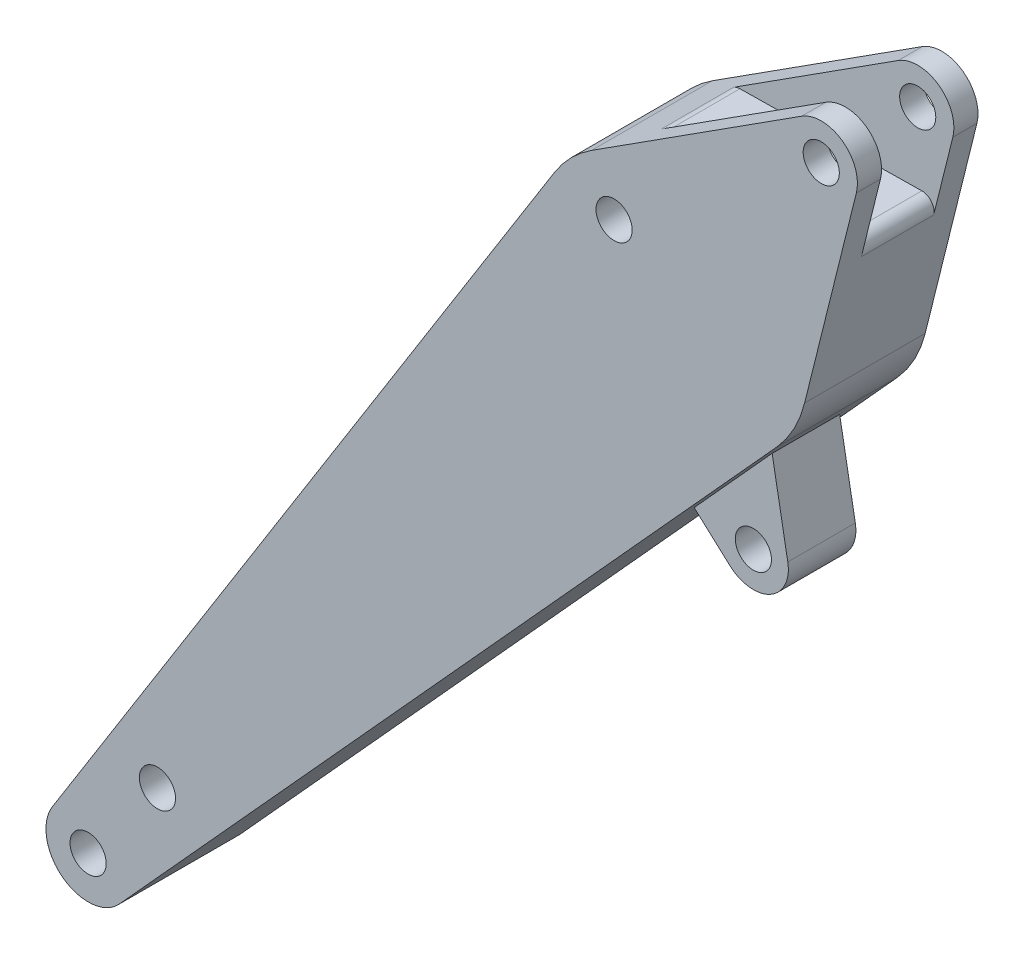
SolidWorks part; units mm, degrees
ref_plane "前视基准面" through (0, 0, 0) normal (0, 0, 1) x (1, 0, 0)
ref_plane "上视基准面" through (0, 0, 0) normal (0, 1, 0) x (1, 0, 0)
ref_plane "右视基准面" through (0, 0, 0) normal (1, 0, 0) x (0, 0, -1)
sketch "草图1" plane through (0, 0, 0) normal (0, 0, 1) x (1, 0, 0)
  line L0 (84.9524, 101.1252) -> (168.9456, 46.856) construction
  line L1 (255.3141, 96.6057) -> (199.0919, 34.648)
  line L2 (255.3141, 96.6057) -> (260.2111, 116.2752)
  line L3 (255.6812, 119.5257) -> (236.3769, 107.1531)
  line L4 (236.3769, 107.1531) -> (193.5351, 38.8599)
  line L5 (257.3, 117) -> (196.5, 37) construction
  line L6 (236.3769, 107.1531) -> (244.8958, 100.6787) construction
  line L7 (255.3141, 96.6057) -> (247.3161, 103.8633) construction
  line L8 (196.5, 37) -> (257.3, 37) construction
  line L9 (257.3, 37) -> (257.3, 117) construction
  arc A0 (193.5351, 38.8599) -> (199.0919, 34.648) centre (196.5, 37) ccw
  arc A1 (255.6812, 119.5257) -> (260.2111, 116.2752) centre (257.3, 117) cw
  circle A4 centre (196.5, 37) radius 1.5
  circle A5 centre (202.2483, 44.5635) radius 1.5
  circle A6 centre (257.3, 117) radius 1.5
  circle A7 centre (240.1188, 104.3092) radius 1.5
  dimension "D2" = 3
  dimension "D3" = 16.5
  dimension "D4" = 3
  dimension "D5" = 3.5
  dimension "D1" = 100
  dimension "D6" = 4
  dimension "D7" = 10.7
  dimension "D8" = 10.8
  dimension "D9" = 80
  dimension "D10" = 9.5
  dimension "D11" = 196.5
  dimension "D12" = 37
  dimension "D13" = 60.8
  dimension "D14" = 6
extrude "凸台-拉伸1" add sketch "草图1" along normal blind 5 and the other way blind 5
sketch "草图2" plane through (0, 0, 0) normal (0, 0, 1) x (1, 0, 0)
  line L0 (242.2703, 110.9303) -> (258.938, 111.1614)
  line L1 (255.6812, 119.5257) -> (236.3769, 107.1531) construction
  line L2 (255.3141, 96.6057) -> (260.2111, 116.2752) construction
  line L7 (199.0919, 34.648) -> (255.3141, 96.6057)
  line L8 (255.3141, 96.6057) -> (260.2111, 116.2752)
  line L9 (255.6812, 119.5257) -> (236.3769, 107.1531)
  line L10 (236.3769, 107.1531) -> (193.5351, 38.8599)
  line L11 (199.0919, 34.648) -> (255.3141, 96.6057)
  line L12 (255.3141, 96.6057) -> (260.2111, 116.2752)
  line L13 (255.6812, 119.5257) -> (236.3769, 107.1531)
  line L14 (236.3769, 107.1531) -> (193.5351, 38.8599)
  circle A0 centre (257.3, 117) radius 1.5 construction
  circle A1 centre (257.3, 117) radius 1.5
  arc A4 (193.5351, 38.8599) -> (199.0919, 34.648) centre (196.5, 37) ccw
  arc A6 (260.2111, 116.2752) -> (255.6812, 119.5257) centre (257.3, 117) ccw
  arc A8 (193.5351, 38.8599) -> (199.0919, 34.648) centre (196.5, 37) ccw
  arc A10 (260.2111, 116.2752) -> (255.6812, 119.5257) centre (257.3, 117) ccw
  dimension "D2" = 7
  dimension "D3" = 15
  dimension "D1" = 0
extrude "切除-拉伸1" cut sketch "草图2" against normal blind 3 and the other way blind 3 contours L12 A10 L13 L0 A1 region at (253.3987, 114.3214, 0)
sketch "草图3" plane through (0, 0, 0) normal (0, 0, 1) x (1, 0, 0)
  line L0 (244.5601, 84.7547) -> (247.5223, 82.0667)
  line L1 (199.0919, 34.648) -> (255.3141, 96.6057) construction
  line L2 (251.0285, 91.8829) -> (252.3246, 84.7315)
  line L3 (244.5601, 84.7547) -> (251.0285, 91.8829)
  circle A0 centre (249.4711, 84.2143) radius 1.5
  arc A1 (247.5223, 82.0667) -> (252.3246, 84.7315) centre (249.4711, 84.2143) ccw
  dimension "D1" = 3
  dimension "D2" = 2.9
  dimension "D3" = 4
extrude "凸台-拉伸4" add sketch "草图3" along normal blind 2.8 and the other way blind 2.8
fillet "圆角1" radius 10 2 edges at (255.3141, 96.6057, 0) (236.3769, 107.1531, 0)
fillet "圆角2" radius 1 2 edges at (258.938, 111.1614, 0) (242.2703, 110.9303, 0)
